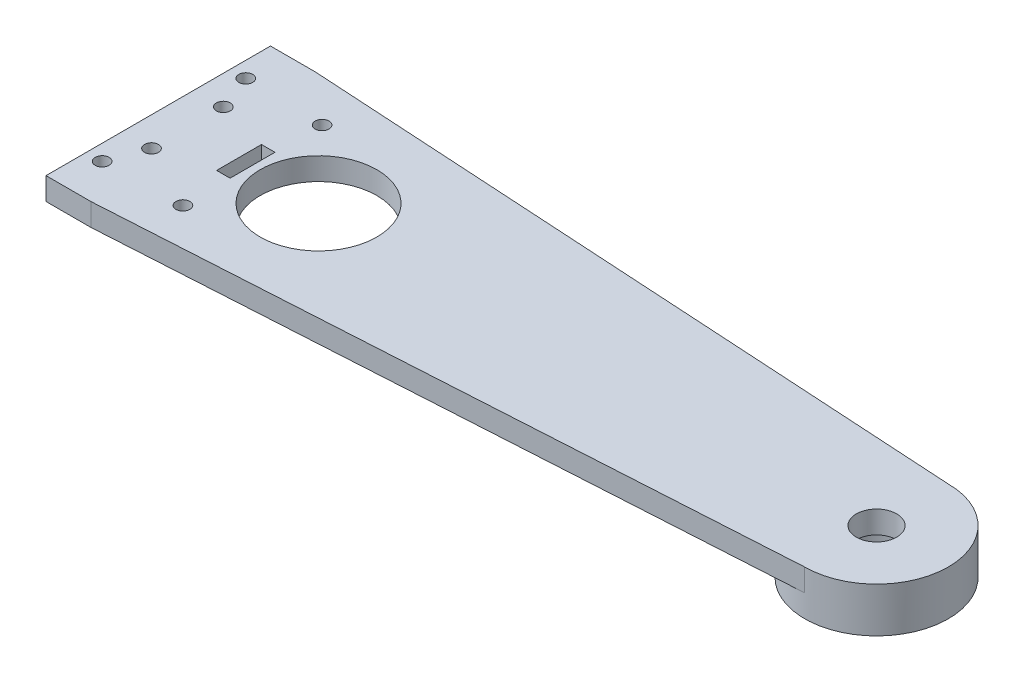
SolidWorks part; units mm, degrees
ref_plane "Front Plane" through (0, 0, 0) normal (0, 0, 1) x (1, 0, 0)
ref_plane "Top Plane" through (0, 0, 0) normal (0, 1, 0) x (1, 0, 0)
ref_plane "Right Plane" through (0, 0, 0) normal (1, 0, 0) x (0, 0, -1)
sketch "Sketch28" plane through (-32, 0, 0) normal (0, -1, 0) x (0, 0, 1)
  line L1 (0, -20.7) -> (0, -145) construction
  line L2 (-8, 8.5) -> (8, 8.5) construction
  line L3 (0, 15) -> (0, -3) construction
  line L8 (-25, 15) -> (25, 15)
  line L12 (25, 15) -> (25, 5)
  line L13 (-25, 15) -> (-25, 5)
  line L14 (-25, 5) -> (-16, -145)
  line L15 (16, -145) -> (25, 5)
  line L16 (-25, 5) -> (-25, 8.5) construction
  line L17 (-25, 8.5) -> (-8, 8.5) construction
  line L18 (-25, 15) -> (-25, 11.5) construction
  line L19 (-25, 11.5) -> (-16, 11.5) construction
  line L20 (-16, 11.5) -> (16, 11.5) construction
  line L21 (-5, -3) -> (5, -3)
  line L26 (5, -3) -> (5, -6)
  line L27 (5, -6) -> (-5, -6)
  line L28 (-5, -6) -> (-5, -3)
  line L29 (-5, -3) -> (-15.5, -3) construction
  line L30 (-15.5, -3) -> (-15.5, -6) construction
  line L31 (5, -3) -> (15.5, -3) construction
  line L32 (15.5, -3) -> (15.5, -6) construction
  line L33 (0, -20.7) -> (0, -6) construction
  circle A7 centre (8, 8.5) radius 1.55
  circle A8 centre (-8, 8.5) radius 1.55
  circle A9 centre (16, 11.5) radius 1.55
  circle A10 centre (-16, 11.5) radius 1.55
  circle A13 centre (-15.5, -6) radius 1.55
  circle A14 centre (15.5, -6) radius 1.55
  circle A15 centre (0, -20.7) radius 12.5 construction
  arc A17 (-16, -145) -> (16, -145) centre (0, -145) ccw
  circle A18 centre (0, -20.7) radius 13
  circle A19 centre (0, -145) radius 4.5
  point P13 (0, 15)
  point P27 (0, -3)
extrude "Boss-Extrude10" add sketch "Sketch28" along normal blind 5
sketch "Sketch29" plane through (0, -5, 0) normal (0, -1, 0) x (1, 0, 0)
  circle A0 centre (113, 0) radius 16
  circle A1 centre (113, 0) radius 8.2
extrude "Boss-Extrude11" add sketch "Sketch29" along normal blind 5
